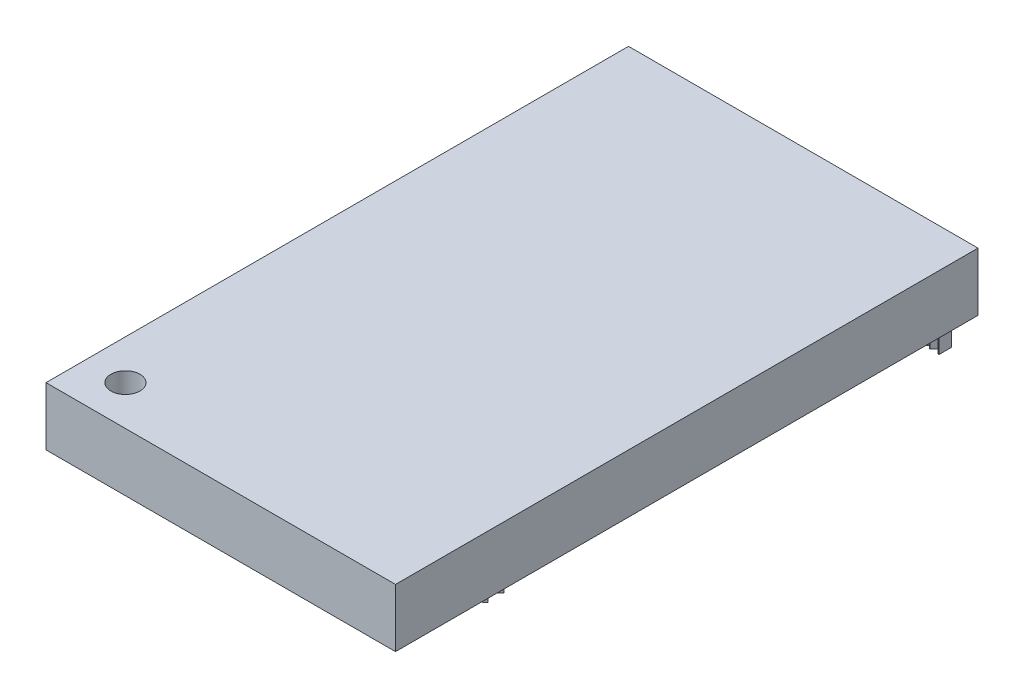
SolidWorks part; units mm, degrees
ref_plane "Front Plane" through (0, 0, 0) normal (0, 0, 1) x (1, 0, 0)
ref_plane "Top Plane" through (0, 0, 0) normal (0, 1, 0) x (1, 0, 0)
ref_plane "Right Plane" through (0, 0, 0) normal (1, 0, 0) x (0, 0, -1)
sketch "Sketch1" plane through (0, 0, 0) normal (0, 1, 0) x (1, 0, 0)
  line L1 (15, -25) -> (-15, -25)
  line L2 (15, -25) -> (15, 25)
  line L3 (15, 25) -> (-15, 25)
  line L4 (-15, -25) -> (-15, 25)
  line L5 (15, -25) -> (-15, 25) construction
  line L6 (15, 25) -> (-15, -25) construction
  point P0 (0, 0)
  dimension "D1" = 30
  dimension "D2" = 50
extrude "Boss-Extrude1" add sketch "Sketch1" along normal blind 5
sketch "Sketch2" plane through (0, 0, 0) normal (0, -1, 0) x (1, 0, 0)
  line L0 (-804.4015, 95.1652) -> (-16.6021, 5.4781) construction
  line L1 (-3.0214, 11.4212) -> (2.4554, 5.4245)
  line L2 (4.2232, 1.6809) -> (5.5403, 1.161)
  line L3 (-4.1653, -14.2986) -> (-6.2104, 0.1558)
  line L4 (-6.1064, 0.1904) -> (-5.7251, -1.1268)
  line L5 (-3.472, 9.6187) -> (-1.0644, 8.9512)
  line L6 (-1.0644, 8.9512) -> (-4.7892, 11.1439)
  line L7 (-4.7892, 11.1439) -> (-3.0214, 11.4212)
  line L9 (2.178, 5.4245) -> (2.4554, 5.4245)
  line L10 (-6.2104, 0.1558) -> (-6.1064, 0.1904)
  circle A0 centre (6.7797, -2.3196) radius 0.0663
  spline S0 degree 3 poles (2.178, 5.4245) (2.3283, 5.3552) (2.5466, 5.3602) (2.6287, 5.2166) (4.3969, 2.1221) (4.6547, 2.9755) (4.2232, 1.6809) knots 0 0 0 0 1 1 1 2 2 2 2
  spline S1 degree 3 poles (5.5403, 1.161) (5.8639, 0.1789) (6.1251, -0.826) (6.5109, -1.7854) (6.5601, -1.9076) (6.7766, -1.9047) (6.8229, -2.028) (7.6734, -4.2924) (9.1799, -6.4723) (9.1799, -8.8912) (9.1799, -10.6584) (8.2332, -12.5752) (6.8229, -13.6401) (4.5521, -15.3546) (1.5241, -15.7171) (-1.1496, -16.6904) (-1.2479, -16.7262) (-1.3796, -16.7207) (-1.4616, -16.6557) (-2.3983, -15.9128) (-3.264, -15.0843) (-4.1653, -14.2986) knots 0 0 0 0 1 1 1 2 2 2 3 3 3 4 4 4 5 5 5 6 6 6 7 7 7 7
  spline S2 degree 3 poles (-5.7251, -1.1268) (-5.182, 1.1032) (-4.5679, 3.3171) (-4.0959, 5.5632) (-3.943, 6.2912) (-3.9096, 7.0399) (-3.8533, 7.7816) (-3.8401, 7.9548) (-3.9382, 8.1353) (-3.888, 8.3015) (-3.7833, 8.6478) (-3.5116, 8.9272) (-3.4027, 9.2721) (-3.3672, 9.3845) (-3.4489, 9.5032) (-3.472, 9.6187) knots 0 0 0 0 1 1 1 2 2 2 3 3 3 4 4 4 5 5 5 5
  point P2 (0, 0)
  point P15 (2.2185, 17.0571)
  point P16 (0, 0)
  point P19 (0, 0)
  point P20 (0, 0)
  point P21 (0, 0)
  point P22 (0, 0)
  point P23 (0, 0)
  point P24 (0, 0)
  point P25 (0, 0)
extrude "Boss-Extrude2" add sketch "Sketch2" along normal blind 2
sketch "Sketch3" plane through (0, 0, 0) normal (0, -1, 0) x (-1, 0, 0)
  line L0 (15, -18.183) -> (-15, -18.183) construction
  line L1 (15, 25) -> (15, -25) construction
  line L2 (-15, -25) -> (-15, 25) construction
  text T0 "SAY NO\r\nTO OCEAN PLASTIC" font "Century Gothic" height in points 8
sketch "Sketch4" plane through (0, 0, 0) normal (0, -1, 0) x (-1, 0, 0)
  line L0 (15, -18.183) -> (8.183, -25) construction
  line L1 (15, -25) -> (-15, -25) construction
  line L2 (15, 25) -> (15, -25) construction
  line L3 (8.183, -25) -> (8.183, -18.183)
  line L4 (15, -18.183) -> (-15, -18.183) construction
  line L5 (8.183, -18.183) -> (15, -25)
  circle A0 centre (11.5915, -21.5915) radius 1.25
  dimension "D2" = 2.5
  dimension "D1" = 45
extrude "Cut-Extrude2" cut sketch "Sketch4" against normal blind 10 contours A0
extrude "Boss-Extrude4" add sketch "Sketch3" along normal blind 2
sketch "Sketch6" plane through (0, 0, 0) normal (0, -1, 0) x (1, 0, 0)
  line L0 (-15, -20.7078) -> (15, -20.7078) construction
  line L1 (-15, -25) -> (-15, 25) construction
  line L2 (15, 25) -> (15, -25) construction
  text T0 "TRASH FOR TRADE\r\nA FUTURE FREE FROM PLASTIC POLLUTION" font "Century Gothic" height in points 4
extrude "Boss-Extrude5" add sketch "Sketch6" along normal blind 2
